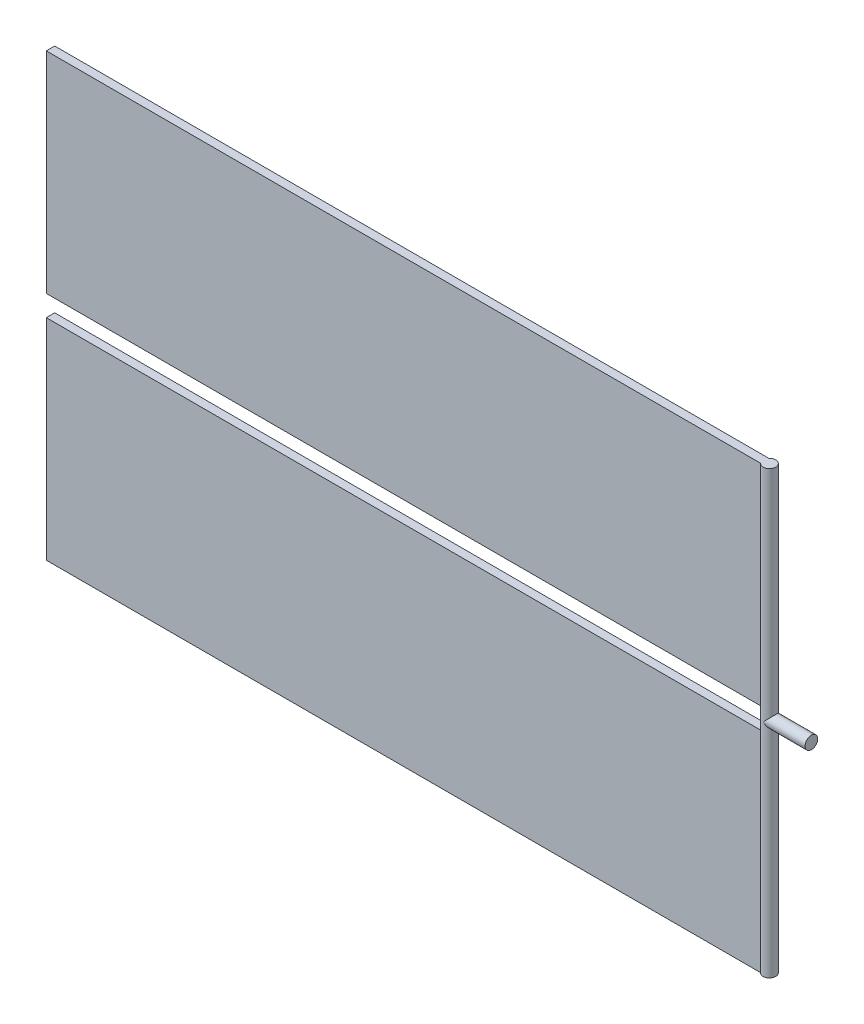
SolidWorks part; units mm, degrees
ref_plane "Front Plane" through (0, 0, 0) normal (0, 0, 1) x (1, 0, 0)
ref_plane "Top Plane" through (0, 0, 0) normal (0, 1, 0) x (1, 0, 0)
ref_plane "Right Plane" through (0, 0, 0) normal (1, 0, 0) x (0, 0, -1)
sketch "Sketch2" plane through (0, 0, 0) normal (0, 0, 1) x (1, 0, 0)
  line L0 (0, 7413.3621) -> (0, -2250.5118) construction
  line L1 (-10896.5007, 0) -> (2741.0055, 0) construction
  line L2 (0, -5250) -> (-17000, -5250)
  line L3 (0, 250) -> (-17000, 250)
  line L4 (0, 250) -> (0, 5250)
  line L5 (0, 5250) -> (-17000, 5250)
  line L6 (-17000, 250) -> (-17000, 5250)
  line L7 (-17000, -250) -> (-17000, -5250)
  line L8 (0, -250) -> (-17000, -250)
  line L9 (0, -250) -> (0, -5250)
  dimension "D1" = 17000
  dimension "D2" = 5000
  dimension "D3" = 250
extrude "Boss-Extrude1" add sketch "Sketch2" along normal blind 100 and the other way blind 100
sketch "Sketch4" plane through (0, 0, 0) normal (0, 1, 0) x (1, 0, 0)
  line L0 (0, 100) -> (0, -100)
  arc A0 (0, -100) -> (0, 100) centre (111.8034, 0) ccw
  dimension "D1" = 300
extrude "Boss-Extrude2" add sketch "Sketch4" along normal blind 5250 and the other way blind 5250
sketch "Sketch5" plane through (0, 0, 0) normal (1, 0, 0) x (0, 0, -1)
  circle A0 centre (0, 0) radius 150
extrude "Boss-Extrude3" add sketch "Sketch5" along normal blind 1000 from offset 111.76
